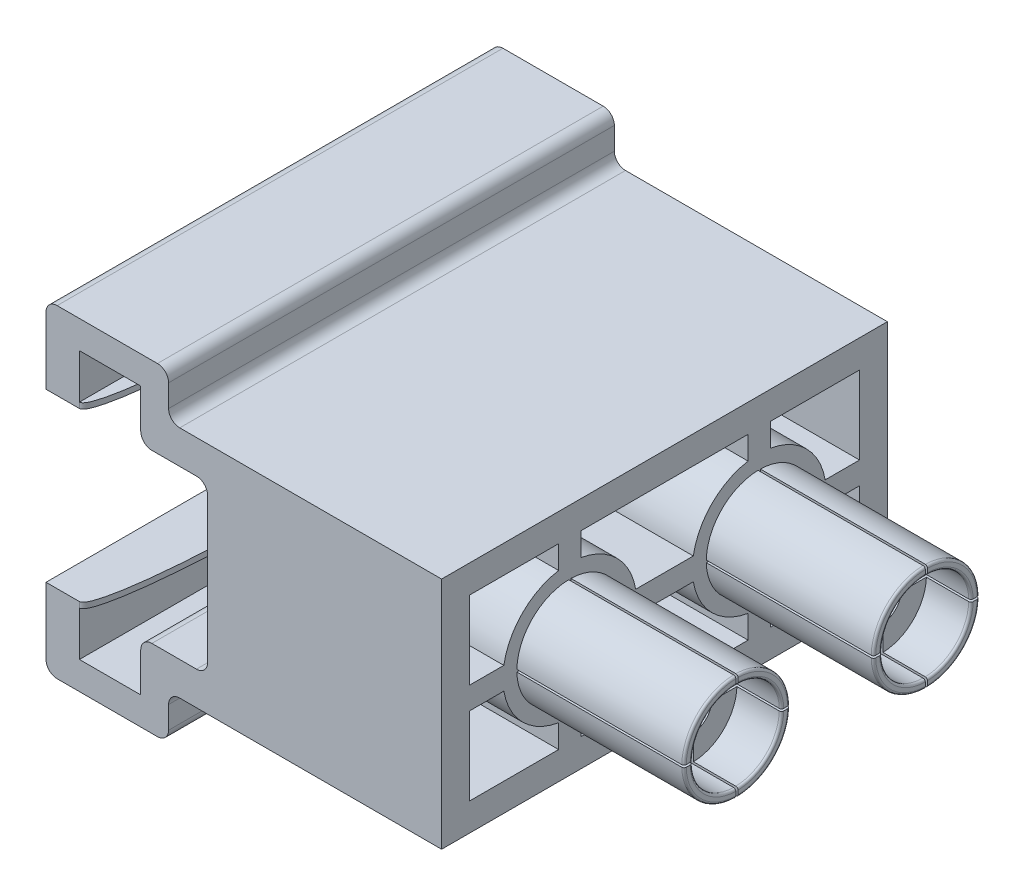
SolidWorks part; units mm, degrees
ref_plane "Płaszczyzna przednia" through (0, 0, 0) normal (0, 0, 1) x (1, 0, 0)
ref_plane "Płaszczyzna górna" through (0, 0, 0) normal (0, 1, 0) x (1, 0, 0)
ref_plane "Płaszczyzna prawa" through (0, 0, 0) normal (1, 0, 0) x (0, 0, -1)
sketch "Szkic1" plane through (0, 0, 0) normal (0, 0, 1) x (1, 0, 0)
  line L0 (35.5, 25) -> (35.5, 4)
  line L1 (35.5, 4) -> (12, 4)
  line L2 (11, 3) -> (11, 1)
  line L3 (10, 0) -> (1, 0)
  line L4 (0, 1) -> (0, 7)
  line L5 (3, 2.5) -> (3, 6.5)
  line L6 (8.5, 2.5) -> (3, 2.5)
  line L7 (8.5, 6) -> (8.5, 2.5)
  line L8 (13.5, 7) -> (9.5, 7)
  line L9 (35.5, 7) -> (11, 7) construction
  line L10 (8.5, 4) -> (8.5, 0) construction
  line L11 (11, 2.5) -> (0, 2.5) construction
  line L12 (3, 0) -> (3, 7) construction
  line L14 (14.5, 21) -> (14.5, 8)
  line L15 (14.5, 14.5) -> (14.5, 4) construction
  line L16 (0, 7) -> (5, 7)
  line L17 (5, 7) -> (5, 6.5)
  line L18 (5, 6.5) -> (3, 6.5)
  line L19 (5, 22.5) -> (3, 22.5)
  line L20 (5, 22) -> (5, 22.5)
  line L21 (0, 22) -> (5, 22)
  line L22 (13.5, 22) -> (9.5, 22)
  line L23 (8.5, 23) -> (8.5, 26.5)
  line L24 (8.5, 26.5) -> (3, 26.5)
  line L25 (3, 26.5) -> (3, 22.5)
  line L26 (0, 28) -> (0, 22)
  line L27 (10, 29) -> (1, 29)
  line L28 (11, 26) -> (11, 28)
  line L29 (35.5, 25) -> (12, 25)
  line L31 (35.5, 14.5) -> (35.5, 4) construction
  line L32 (11, 0) -> (0, 0) construction
  line L33 (0, 0) -> (0, 7) construction
  line L34 (11, 4) -> (11, 0) construction
  line L35 (35.5, 4) -> (11, 4) construction
  arc A0 (8.5, 6) -> (9.5, 7) centre (9.5, 6) cw
  arc A1 (9.5, 22) -> (8.5, 23) centre (9.5, 23) cw
  arc A2 (13.5, 22) -> (14.5, 21) centre (13.5, 21) cw
  arc A3 (14.5, 8) -> (13.5, 7) centre (13.5, 8) cw
  arc A4 (1, 0) -> (0, 1) centre (1, 1) cw
  arc A5 (11, 1) -> (10, 0) centre (10, 1) cw
  arc A6 (12, 4) -> (11, 3) centre (12, 3) ccw
  arc A7 (1, 29) -> (0, 28) centre (1, 28) ccw
  arc A8 (11, 28) -> (10, 29) centre (10, 28) ccw
  arc A9 (12, 25) -> (11, 26) centre (12, 26) cw
  dimension "D3" = 1
  dimension "D2" = 21
  dimension "D11" = 0.5
  dimension "D12" = 5
  dimension "D10" = 21
extrude "Dodanie-wyciągnięcie1" add sketch "Szkic1" along normal blind 40
fillet "Zaokrąglenie4" radius 19 2 edges at (5, 6.75, 0) (5, 6.75, 40) second distance 2 first distance on face at (5, 6.75, 20)
fillet "Zaokrąglenie14" radius 19 1 edges at (5, 22.25, 40) second distance 2 first distance on face at (5, 22.25, 20)
fillet "Zaokrąglenie25" radius 2 1 edges at (5, 22.25, 0) second distance 19 first distance on face at (8.9723, 14.6894, 0)
ref_plane "Płaszczyzna1" through (35.5, 0, 0) normal (1, 0, 0) x (0, 0, -1)
sketch "Szkic2" plane through (35.5, 0, 0) normal (1, 0, 0) x (0, 0, -1)
  line L0 (-2.5, 22.5) -> (-37.5, 22.5)
  line L5 (-37.5, 22.5) -> (-37.5, 6.5)
  line L6 (-2.5, 6.5) -> (-37.5, 6.5)
  line L7 (-2.5, 22.5) -> (-2.5, 6.5)
extrude "Wytnij-wyciągnięcie1" cut sketch "Szkic2" against normal blind 19
sketch "Szkic3" plane through (35.5, 0, 0) normal (1, 0, 0) x (0, 0, -1)
  line L0 (-22.5839, 13.5) -> (-17.4161, 13.5)
  line L3 (-12.5, 22.5) -> (-12.5, 20.4161)
  line L4 (-37.5, 13.5) -> (-34.4161, 13.5)
  line L5 (-27.5, 6.5) -> (-27.5, 8.5839)
  line L8 (-22.5839, 15.5) -> (-17.4161, 15.5)
  line L9 (-27.5, 20.4161) -> (-27.5, 22.5)
  line L10 (-10.5, 22.5) -> (-10.5, 20.4161)
  line L11 (-37.5, 15.5) -> (-34.4161, 15.5)
  line L12 (-29.5, 6.5) -> (-29.5, 8.5839)
  line L13 (-29.5, 20.4161) -> (-29.5, 22.5)
  line L14 (-10.5, 22.5) -> (-12.5, 22.5)
  line L15 (-12.5, 8.5839) -> (-12.5, 6.5)
  line L16 (-10.5, 8.5839) -> (-10.5, 6.5)
  line L17 (-5.5839, 13.5) -> (-2.5, 13.5)
  line L18 (-5.5839, 15.5) -> (-2.5, 15.5)
  line L19 (-2.5, 15.5) -> (-2.5, 13.5)
  line L20 (-10.5, 6.5) -> (-12.5, 6.5)
  line L21 (-27.5, 6.5) -> (-29.5, 6.5)
  line L22 (-37.5, 13.5) -> (-37.5, 15.5)
  line L23 (-29.5, 22.5) -> (-27.5, 22.5)
  arc A0 (-17.4161, 13.5) -> (-12.5, 8.5839) centre (-11.5, 14.5) ccw
  arc A1 (-27.5, 8.5839) -> (-22.5839, 13.5) centre (-28.5, 14.5) ccw
  arc A2 (-22.5839, 15.5) -> (-27.5, 20.4161) centre (-28.5, 14.5) ccw
  arc A3 (-29.5, 20.4161) -> (-34.4161, 15.5) centre (-28.5, 14.5) ccw
  arc A4 (-34.4161, 13.5) -> (-29.5, 8.5839) centre (-28.5, 14.5) ccw
  arc A5 (-10.5, 8.5839) -> (-5.5839, 13.5) centre (-11.5, 14.5) ccw
  arc A6 (-5.5839, 15.5) -> (-10.5, 20.4161) centre (-11.5, 14.5) ccw
  arc A7 (-12.5, 20.4161) -> (-17.4161, 15.5) centre (-11.5, 14.5) ccw
extrude "Dodanie-wyciągnięcie2" add sketch "Szkic3" along direction (-1, 0, 0) on the side against the normal blind 19
sketch "Szkic4" plane through (35.5, 0, 0) normal (1, 0, 0) x (0, 0, -1)
  circle A0 centre (-28.5, 14.5) radius 2.5
  circle A1 centre (-11.5, 14.5) radius 2.5
extrude "Wytnij-wyciągnięcie2" cut sketch "Szkic4" against normal blind 22 contours A1 | A0 region at (35.5, 14.5, 11.5)
ref_plane "Płaszczyzna2" through (14.5, 0, 0) normal (-1, 0, 0) x (0, 0, 1)
sketch "Szkic5" plane through (14.5, 0, 0) normal (-1, 0, 0) x (0, 0, 1)
  line L0 (21.25, 5.6256) -> (21.25, 23.3465)
  line L1 (18.75, 23.3465) -> (21.25, 23.3465)
  line L4 (18.75, 5.6256) -> (18.75, 23.3465)
  line L5 (21.25, 5.6256) -> (18.75, 5.6256)
extrude "Dodanie-wyciągnięcie3" add sketch "Szkic5" along normal blind 6 contours L4 L1 L0 L5
sketch "Szkic6" plane through (35.5, 0, 0) normal (1, 0, 0) x (0, 0, -1)
  line L0 (-11.4, 12.7529) -> (-11.4, 9.7511)
  line L1 (-11.6, 12.7529) -> (-11.6, 9.7511)
  line L2 (-9.7529, 14.4) -> (-6.7511, 14.4)
  line L3 (-28.6, 19.2489) -> (-28.6, 16.2471)
  line L4 (-33.2489, 14.4) -> (-30.2471, 14.4)
  line L5 (-11.6, 19.2489) -> (-11.6, 16.2471)
  line L6 (-28.4, 19.2489) -> (-28.4, 16.2471)
  line L7 (-33.2489, 14.6) -> (-30.2471, 14.6)
  line L8 (-11.4, 19.2489) -> (-11.4, 16.2471)
  line L9 (-9.7529, 14.6) -> (-6.7511, 14.6)
  line L10 (-16.2489, 14.6) -> (-13.2471, 14.6)
  line L11 (-16.2489, 14.4) -> (-13.2471, 14.4)
  line L12 (-26.7529, 14.6) -> (-23.7511, 14.6)
  line L13 (-26.7529, 14.4) -> (-23.7511, 14.4)
  line L14 (-28.4, 12.7529) -> (-28.4, 9.7511)
  line L15 (-28.6, 12.7529) -> (-28.6, 9.7511)
  arc A0 (-28.6, 19.2489) -> (-33.2489, 14.6) centre (-28.5, 14.5) ccw
  arc A1 (-11.4, 9.7511) -> (-6.7511, 14.4) centre (-11.5, 14.5) ccw
  arc A2 (-6.7511, 14.6) -> (-11.4, 19.2489) centre (-11.5, 14.5) ccw
  arc A3 (-11.6, 19.2489) -> (-16.2489, 14.6) centre (-11.5, 14.5) ccw
  arc A4 (-16.2489, 14.4) -> (-11.6, 9.7511) centre (-11.5, 14.5) ccw
  arc A5 (-23.7511, 14.6) -> (-28.4, 19.2489) centre (-28.5, 14.5) ccw
  arc A6 (-28.4, 9.7511) -> (-23.7511, 14.4) centre (-28.5, 14.5) ccw
  arc A7 (-33.2489, 14.4) -> (-28.6, 9.7511) centre (-28.5, 14.5) ccw
  arc A8 (-26.7529, 14.6) -> (-28.4, 16.2471) centre (-28.5, 14.5) ccw
  arc A9 (-9.7529, 14.6) -> (-11.4, 16.2471) centre (-11.5, 14.5) ccw
  arc A10 (-28.6, 16.2471) -> (-30.2471, 14.6) centre (-28.5, 14.5) ccw
  arc A11 (-30.2471, 14.4) -> (-28.6, 12.7529) centre (-28.5, 14.5) ccw
  arc A12 (-28.4, 12.7529) -> (-26.7529, 14.4) centre (-28.5, 14.5) ccw
  arc A13 (-11.4, 12.7529) -> (-9.7529, 14.4) centre (-11.5, 14.5) ccw
  arc A14 (-13.2471, 14.4) -> (-11.6, 12.7529) centre (-11.5, 14.5) ccw
  arc A15 (-11.6, 16.2471) -> (-13.2471, 14.6) centre (-11.5, 14.5) ccw
extrude "Dodanie-wyciągnięcie4" add sketch "Szkic6" along normal blind 15
chamfer "Sfazowanie1" distance 2 angle 45 8 edges at (35.5, 15.7374, 29.7374) (35.5, 13.2626, 29.7374) (35.5, 13.2626, 27.2626) (35.5, 15.7374, 27.2626) (35.5, 13.2626, 12.7374) (35.5, 13.2626, 10.2626) (35.5, 15.7374, 10.2626) (35.5, 15.7374, 12.7374)
ref_plane "Płaszczyzna3" through (50.5, 0, 0) normal (1, 0, 0) x (0, 0, -1)
sketch "Szkic8" plane through (50.5, 0, 0) normal (1, 0, 0) x (0, 0, -1)
  circle A0 centre (-28.5, 14.5) radius 4
  circle A1 centre (-11.5, 14.5) radius 4
extrude "Wytnij-wyciągnięcie3" cut sketch "Szkic8" against normal blind 4
fillet "Zaokrąglenie26" radius 0.2 16 edges at (50.5, 11.1412, 14.8588) (50.5, 11.6716, 14.3284) (50.5, 11.1412, 8.1412) (50.5, 11.6716, 8.6716) (50.5, 17.3284, 8.6716) (50.5, 17.8588, 8.1412) (50.5, 17.8588, 14.8588) (50.5, 17.3284, 14.3284) (50.5, 11.6716, 31.3284) (50.5, 11.1412, 31.8588) (50.5, 11.1412, 25.1412) (50.5, 11.6716, 25.6716) (50.5, 17.3284, 25.6716) (50.5, 17.8588, 25.1412) (50.5, 17.3284, 31.3284) (50.5, 17.8588, 31.8588)
